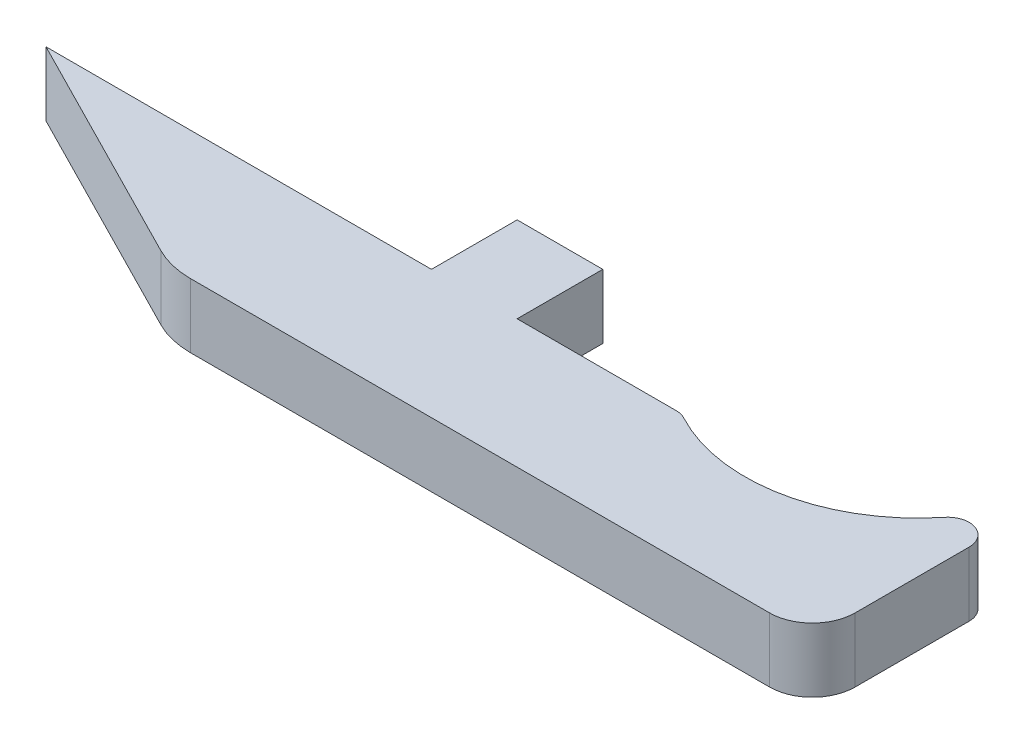
SolidWorks part; units mm, degrees
material "AISI 4130 Steel, annealed at 865C"
ref_plane "X-Y Datum" through (0, 0, 0) normal (0, 0, 1) x (1, 0, 0)
ref_plane "X-Z Datum" through (0, 0, 0) normal (0, 1, 0) x (1, 0, 0)
ref_plane "Y-Z Datum" through (0, 0, 0) normal (1, 0, 0) x (0, 0, -1)
sketch "Sketch1" plane through (0, 0, 0) normal (0, 1, 0) x (1, 0, 0)
  line L0 (59.0296, -11.6201) -> (59.0296, 13.7799) construction
  line L1 (59.0296, -10.0453) -> (3.302, -10.0453)
  line L2 (59.0296, -10.0453) -> (59.0296, 1.0799)
  line L3 (24.2316, -19.5703) -> (71.8566, -19.5703)
  line L4 (71.8566, 1.0799) -> (71.8566, -19.5703)
  line L5 (5.5225, -10.0453) -> (24.2316, -19.5703)
  line L7 (34.0975, -10.0326) -> (2.3475, -10.0326) construction
  line L8 (34.0975, -10.0326) -> (2.3475, -10.0326)
  circle A0 centre (59.0296, 1.0799) radius 12.827
  spline S0 degree 3 poles (59.0296, -11.6201) (33.6296, -11.6201) (33.6296, 13.7799) (59.0296, 13.7799) (84.4296, 13.7799) (84.4296, -11.6201) (59.0296, -11.6201) (33.6296, -11.6201) (33.6296, 13.7799) knots -0.5 0 0 0 0.5 0.5 0.5 1 1 1 1.5 1.5 1.5 weights 1 0.333333 0.333333 1 0.333333 0.333333 1 0.333333 0.333333 only from (59.0296, -11.6201) to (59.0296, -11.6201)
  spline S1 degree 3 poles (59.0296, -11.6201) (33.6296, -11.6201) (33.6296, 13.7799) (59.0296, 13.7799) (84.4296, 13.7799) (84.4296, -11.6201) (59.0296, -11.6201) (33.6296, -11.6201) (33.6296, 13.7799) knots -0.5 0 0 0 0.5 0.5 0.5 1 1 1 1.5 1.5 1.5 weights 1 0.333333 0.333333 1 0.333333 0.333333 1 0.333333 0.333333 only from (59.0296, -11.6201) to (59.0296, -11.6201) construction
  dimension "D3" = 25.654
  dimension "D5" = 9.525
  dimension "D1" = 55.7276
  dimension "D2" = 11.1252
  dimension "D4" = 3.175
  dimension "D6" = 47.625
extrude "Boss-Extrude1" add sketch "Sketch1" along normal blind 4.7625 contours L1 A0 region at (43.7069, 0, 14.379)
fillet "Fillet1" radius 1.5875 2 edges at (52.6451, 2.3813, 10.0453) (71.8566, 2.3813, -1.0799)
fillet "Fillet2" radius 6.35 1 edges at (24.2316, 2.3813, 19.5703)
fillet "Fillet3" radius 3.175 1 edges at (71.8566, 2.3813, 19.5703)
sketch "Sketch6" plane through (0, 0, 10.0453) normal (0, 0, -1) x (-1, 0, 0)
  line L0 (-52.2351, 4.7625) -> (-5.5225, 4.7625) construction
  line L1 (-40.4475, 4.7625) -> (-34.0975, 4.7625)
  line L2 (-40.4475, 4.7625) -> (-40.4475, 0)
  line L3 (-40.4475, 0) -> (-34.0975, 0)
  line L4 (-34.0975, 4.7625) -> (-34.0975, 0)
  line L5 (-52.2351, 0) -> (-5.5225, 0) construction
  line L6 (-5.5225, 4.7625) -> (-5.5225, 0) construction
  dimension "D1" = 6.35
  dimension "D2" = 28.575
extrude "Boss-Extrude2" add sketch "Sketch6" along normal blind 6.35
